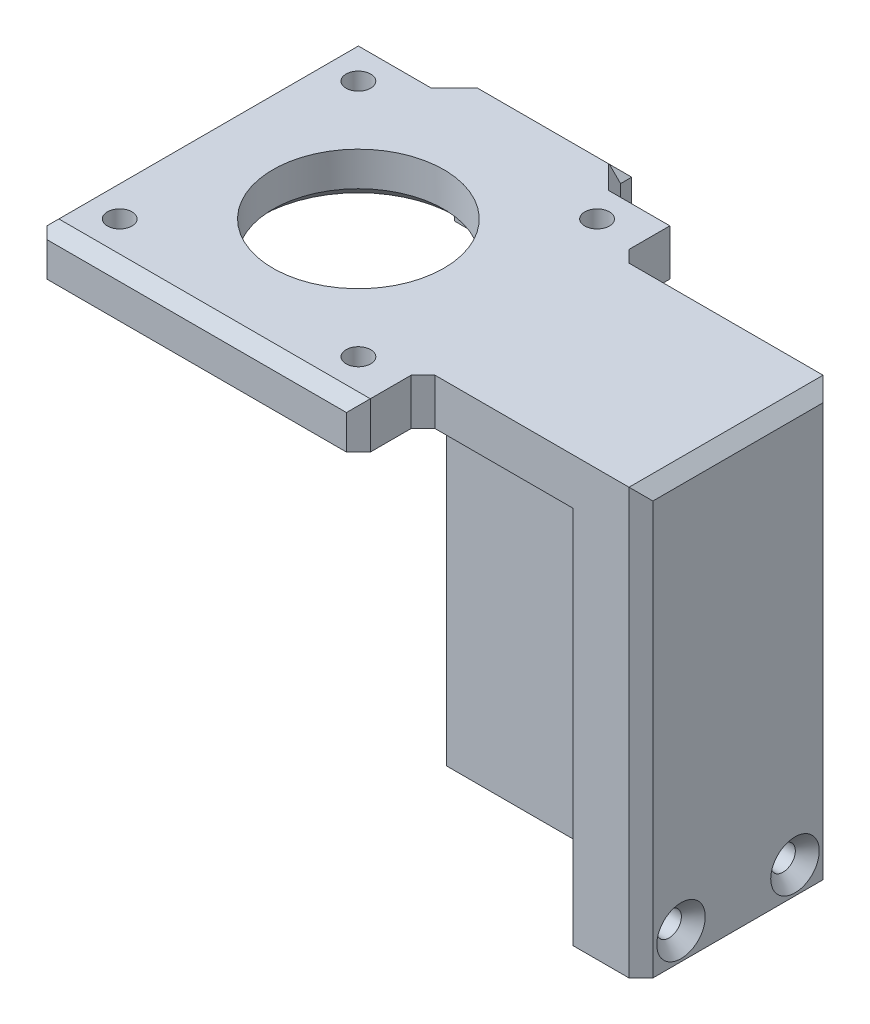
SolidWorks part; units mm, degrees
ref_plane "Front Plane" through (0, 0, 0) normal (0, 0, 1) x (1, 0, 0)
ref_plane "Top Plane" through (0, 0, 0) normal (0, 1, 0) x (1, 0, 0)
ref_plane "Right Plane" through (0, 0, 0) normal (1, 0, 0) x (0, 0, -1)
sketch "Sketch1" plane through (0, 0, 0) normal (0, 0, 1) x (1, 0, 0)
  line L0 (0, 0) -> (0, 11)
  line L1 (0, 11) -> (-19, 11)
  line L2 (0, 0) -> (8.8, 0)
  line L3 (8.8, 0) -> (8.8, 49.2)
  line L4 (8.8, 49.2) -> (-19, 49.2)
  line L5 (-19, 49.2) -> (-19, 11)
  dimension "D1" = 11
  dimension "D2" = 19
  dimension "D3" = 8.8
  dimension "D4" = 38.2
extrude "Boss-Extrude1" add sketch "Sketch1" along normal blind 25.2 contours L4 L5 L1 L0 L2 L3
sketch "Sketch2" plane through (0, 49.2, 0) normal (0, 1, 0) x (1, 0, 0)
  line L0 (8.8, -12.6) -> (-40.5, -12.6) construction
  line L2 (-40.5, 8.4) -> (-40.5, -33.6) construction
  line L3 (-61.5, 8.4) -> (-19.5, 8.4)
  line L4 (8.8, 0) -> (-19, 0)
  line L5 (-19, 0) -> (-19, -25.2)
  line L6 (-19, -25.2) -> (8.8, -25.2)
  line L7 (8.8, -25.2) -> (8.8, 0)
  line L8 (8.8, 0) -> (-19.5, 0)
  line L11 (8.8, -25.2) -> (8.8, 0)
  line L12 (-61.5, 8.4) -> (-61.5, -33.6)
  line L13 (-61.5, -33.6) -> (-19.5, -33.6)
  line L14 (-19.5, 8.4) -> (-19.5, 0)
  line L15 (-61.5, 8.4) -> (-19.5, -33.6) construction
  line L16 (-61.5, -33.6) -> (-19.5, 8.4) construction
  line L17 (-19.5, -25.2) -> (8.8, -25.2)
  line L18 (-19.5, -25.2) -> (-19.5, -33.6)
  circle A0 centre (-56, 2.9) radius 1.6
  circle A1 centre (-56, -28.1) radius 1.6
  circle A2 centre (-25, -28.1) radius 1.6
  circle A3 centre (-25, 2.9) radius 1.6
  dimension "D5" = 3.2
  dimension "D2" = 40.5
  dimension "D3" = 42
  dimension "D4" = 42
  dimension "D6" = 15.5
  dimension "D1" = 0
extrude "Boss-Extrude2" add sketch "Sketch2" along normal blind 6
sketch "Sketch3" plane through (0, 11, 0) normal (0, -1, 0) x (1, 0, 0)
  line L0 (-19, 24.2) -> (0, 24.2)
  line L1 (-19, 25.2) -> (0, 25.2)
  line L2 (-19, 25.2) -> (-19, 0)
  line L3 (-19, 0) -> (0, 0)
  line L4 (0, 25.2) -> (0, 0)
  line L5 (0, 1) -> (-19, 1)
  line M7 (-19, 0) -> (0, 0)
  line M8 (0, 0) -> (0, 25.2)
  line M9 (0, 25.2) -> (-19, 25.2)
  line M10 (-19, 25.2) -> (-19, 0)
  dimension "D1" = 1
  dimension "D2" = 1
extrude "Cut-Extrude1" cut sketch "Sketch3" against normal up to surface (38.2 mm away) contours L0 M10 M8 M9 | L5 L2 M8 M7 up to face at (-29.875, 49.2, 12.6)
chamfer "Chamfer2" distance 1.55 angle 45 4 edges at (-57.6, 49.2, -2.9) (-23.4, 49.2, -2.9) (-26.6, 49.2, 28.1) (-54.4, 49.2, 28.1)
sketch "Sketch4" plane through (0, 49.2, 0) normal (0, -1, 0) x (1, 0, 0)
  line L0 (-40.5, 33.6) -> (-40.5, -8.4) construction
  line L1 (-61.5, 33.6) -> (-19.5, 33.6) construction
  line L2 (-19.5, -8.4) -> (-61.5, -8.4) construction
  line L3 (-61.5, 12.6) -> (-40.5, 12.6) construction
  line L4 (-61.5, -8.4) -> (-61.5, 33.6) construction
  circle A0 centre (-40.5, 12.6) radius 11.1
  dimension "D1" = 22.2
extrude "Cut-Extrude2" cut sketch "Sketch4" against normal through all
chamfer "Chamfer3" distance 1.55 angle 45 16 edges at (-19, 30.1, 1) (-19, 30.1, 24.2) (8.8, 27.6, 0) (8.8, 27.6, 25.2) (8.8, 55.2, 12.6) (-19.5, 52.2, 0) (-61.5, 52.2, -8.4) (-61.5, 55.2, 12.6) (-61.5, 52.2, 33.6) (-19.5, 52.2, -8.4) (-40.5, 49.2, -8.4) (-61.5, 49.2, 12.6) (-40.5, 49.2, 33.6) (-19.5, 52.2, 33.6) (-19.5, 52.2, 25.2) (-29.4, 49.2, 12.6)
chamfer "Chamfer4" distance 1 angle 45 2 edges at (0, 30.1, 24.2) (0, 30.1, 1)
sketch "Sketch5" plane through (8.8, 0, 0) normal (1, 0, 0) x (0, 0, -1)
  line L0 (-23.65, 0) -> (-1.55, 0) construction
  line L1 (-12.6, 0) -> (-12.6, 53.65) construction
  line L2 (-1.55, 53.65) -> (-23.65, 53.65) construction
  circle A0 centre (-12.6, 3.5) radius 1.6
  circle A1 centre (-5.2, 3.5) radius 1.6
  circle A2 centre (-20, 3.5) radius 1.6
  dimension "D1" = 3.2
  dimension "D2" = 3.5
  dimension "D3" = 2
extrude "Cut-Extrude3" cut sketch "Sketch5" against normal through all contours A2 | A1
chamfer "Chamfer5" distance 1.55 angle 45 2 edges at (8.8, 3.5, 3.6) (8.8, 3.5, 21.6)
sketch "Sketch6" plane through (0, 0, 33.6) normal (0, 0, 1) x (1, 0, 0)
  line L0 (-59.95, 55.2) -> (-21.05, 55.2) construction
  line L1 (-49, 55.2) -> (-29, 55.2)
  line L2 (-49, 55.2) -> (-49, 40.2)
  line L3 (-49, 40.2) -> (-29, 40.2)
  line L4 (-29, 55.2) -> (-29, 40.2)
  line L5 (-19, 11) -> (-19, 49.2) construction
  dimension "D1" = 10
  dimension "D2" = 20
  dimension "D3" = 15
extrude "Boss-Extrude3" add sketch "Sketch6" against normal blind 3 from surface at -42 starting at face at (-40.5, 52.2, -8.4)
sketch "Sketch7" plane through (0, 0, -11.4) normal (0, 0, -1) x (-1, 0, 0)
  line L0 (39, 55.2) -> (39, 40.2) construction
  line L1 (29, 55.2) -> (49, 55.2) construction
  line L2 (49, 40.2) -> (29, 40.2) construction
  line L3 (49, 45.2) -> (29, 45.2) construction
  line L4 (49, 55.2) -> (49, 40.2) construction
  line L5 (29, 40.2) -> (29, 55.2) construction
  circle A0 centre (44, 45.2) radius 0.9
  circle A1 centre (34, 45.2) radius 0.9
  dimension "D2" = 1.8
  dimension "D3" = 1.8
  dimension "D1" = 5
  dimension "D4" = 10
extrude "Cut-Extrude4" cut sketch "Sketch7" against normal through all
chamfer "Chamfer7" distance 1.55 angle 45 7 edges at (-40.5, 55.2, 33.6) (-29, 55.2, -9.9) (-49, 55.2, -9.9) (-29, 52.2, -8.4) (-25.025, 55.2, -8.4) (-49, 52.2, -8.4) (-54.475, 55.2, -8.4)
chamfer "Chamfer8" distance 1.55 angle 45 1 edges at (-39, 55.2, -11.4)
